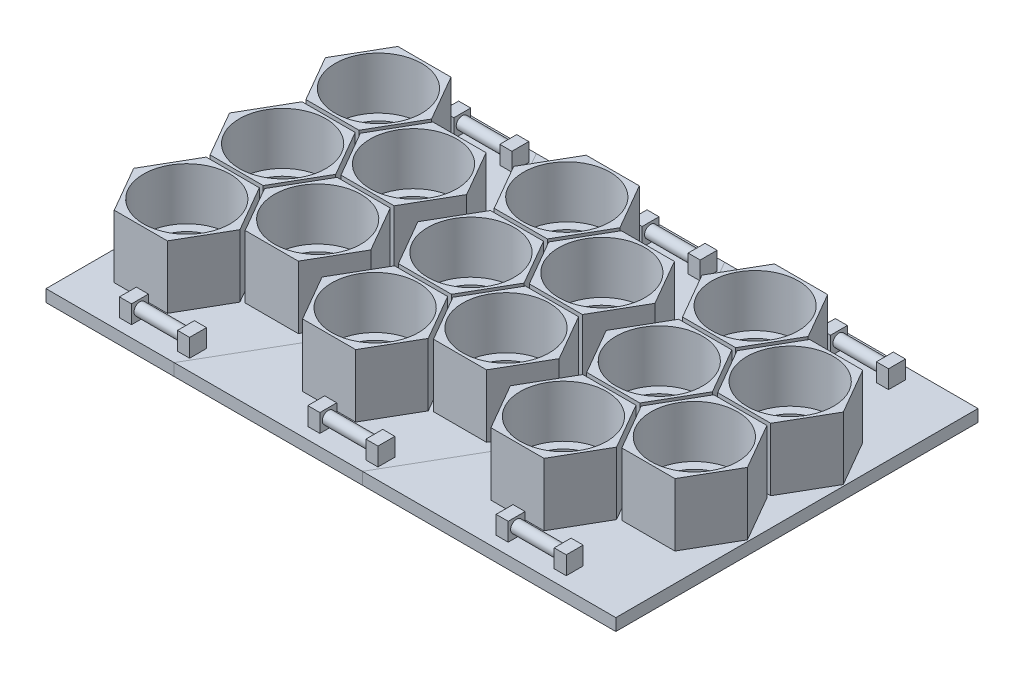
SolidWorks part; units mm, degrees
ref_plane "Front Plane" through (0, 0, 0) normal (0, 0, 1) x (1, 0, 0)
ref_plane "Top Plane" through (0, 0, 0) normal (0, 1, 0) x (1, 0, 0)
ref_plane "Right Plane" through (0, 0, 0) normal (1, 0, 0) x (0, 0, -1)
sketch "Sketch1" plane through (0, 0, 0) normal (0, 1, 0) x (1, 0, 0)
  line L0 (-118, 0) -> (118, 0)
  line L1 (-118, -75) -> (-118, 75)
  line L2 (118, -75) -> (118, 75)
  line L3 (-118, 75) -> (118, 75)
  line L4 (118, -75) -> (-118, -75)
  point P4 (0, 0)
  point P8 (-118, 0)
  point P11 (118, 0)
  dimension "D1" = 236
  dimension "D2" = 150
  dimension "D3" = 150
extrude "Boss-Extrude1" add sketch "Sketch1" along normal mid plane 5 contours L4 L2 L0 L1 | L3 L1 L0 L2 region at (0, 0, -37.5) region at (0, 0, 37.5)
sketch "Sketch3" plane through (0, 2.5, 0) normal (0, 1, 0) x (1, 0, 0)
  line L1 (-84.0015, 58.7375) -> (-105.9985, 58.7375)
  line L2 (-105.9985, 58.7375) -> (-116.997, 39.6875)
  line L3 (-116.997, 39.6875) -> (-105.9985, 20.6375)
  line L4 (-105.9985, 20.6375) -> (-84.0015, 20.6375)
  line L5 (-84.0015, 20.6375) -> (-73.003, 39.6875)
  line L6 (-73.003, 39.6875) -> (-84.0015, 58.7375)
  line L7 (-84.0015, 19.05) -> (-105.9985, 19.05)
  line L8 (-105.9985, 19.05) -> (-116.997, 0)
  line L9 (-116.997, 0) -> (-105.9985, -19.05)
  line L10 (-105.9985, -19.05) -> (-84.0015, -19.05)
  line L11 (-84.0015, -19.05) -> (-73.003, 0)
  line L12 (-73.003, 0) -> (-84.0015, 19.05)
  line L13 (-73.003, -39.6875) -> (-84.0015, -20.6375)
  line L14 (-84.0015, -20.6375) -> (-105.9985, -20.6375)
  line L15 (-105.9985, -20.6375) -> (-116.997, -39.6875)
  line L16 (-116.997, -39.6875) -> (-105.9985, -58.7375)
  line L17 (-105.9985, -58.7375) -> (-84.0015, -58.7375)
  line L18 (-84.0015, -58.7375) -> (-73.003, -39.6875)
  line L31 (-95, -19.05) -> (-95, -20.6375) construction
  line L32 (-105.9985, -58.7375) -> (-116.997, -39.6875)
  line L33 (-73.003, -39.6875) -> (-84.0015, -58.7375)
  line L34 (-84.0015, -20.6375) -> (-73.003, -39.6875)
  line L35 (-116.997, -39.6875) -> (-105.9985, -20.6375)
  line L36 (-116.997, 0) -> (-105.9985, 19.05)
  line L37 (-105.9985, -19.05) -> (-116.997, 0)
  line L38 (-73.003, 0) -> (-84.0015, -19.05)
  line L39 (-84.0015, 19.05) -> (-73.003, 0)
  line L40 (-116.997, 39.6875) -> (-105.9985, 58.7375)
  line L41 (-105.9985, 20.6375) -> (-116.997, 39.6875)
  line L42 (-73.003, 39.6875) -> (-84.0015, 20.6375)
  line L43 (-84.0015, 58.7375) -> (-73.003, 39.6875)
  line L44 (-105.9985, 58.7375) -> (-116.997, 39.6875)
  line L45 (-116.997, 39.6875) -> (-105.9985, 20.6375)
  line L46 (-84.0015, 20.6375) -> (-73.003, 39.6875)
  line L47 (-73.003, 39.6875) -> (-84.0015, 58.7375)
  line L48 (-105.9985, 19.05) -> (-116.997, 0)
  line L49 (-116.997, 0) -> (-105.9985, -19.05)
  line L50 (-84.0015, -19.05) -> (-73.003, 0)
  line L51 (-73.003, 0) -> (-84.0015, 19.05)
  line L52 (-73.003, -39.6875) -> (-84.0015, -20.6375)
  line L53 (-105.9985, -20.6375) -> (-116.997, -39.6875)
  line L54 (-116.997, -39.6875) -> (-105.9985, -58.7375)
  line L55 (-84.0015, -58.7375) -> (-73.003, -39.6875)
  line L56 (-105.9985, -58.7375) -> (-116.997, -39.6875)
  line L57 (-73.003, -39.6875) -> (-84.0015, -58.7375)
  line L58 (-84.0015, -20.6375) -> (-73.003, -39.6875)
  line L59 (-116.997, -39.6875) -> (-105.9985, -20.6375)
  line L60 (-116.997, 0) -> (-105.9985, 19.05)
  line L61 (-105.9985, -19.05) -> (-116.997, 0)
  line L62 (-73.003, 0) -> (-84.0015, -19.05)
  line L63 (-84.0015, 19.05) -> (-73.003, 0)
  line L64 (-116.997, 39.6875) -> (-105.9985, 58.7375)
  line L65 (-105.9985, 20.6375) -> (-116.997, 39.6875)
  line L66 (-73.003, 39.6875) -> (-84.0015, 20.6375)
  line L67 (-84.0015, 58.7375) -> (-73.003, 39.6875)
  line L68 (-105.9985, 58.7375) -> (-116.997, 39.6875)
  line L69 (-116.997, 39.6875) -> (-105.9985, 20.6375)
  line L70 (-84.0015, 20.6375) -> (-73.003, 39.6875)
  line L71 (-73.003, 39.6875) -> (-84.0015, 58.7375)
  line L72 (-105.9985, 19.05) -> (-116.997, 0)
  line L73 (-116.997, 0) -> (-105.9985, -19.05)
  line L74 (-84.0015, -19.05) -> (-73.003, 0)
  line L75 (-73.003, 0) -> (-84.0015, 19.05)
  line L76 (-73.003, -39.6875) -> (-84.0015, -20.6375)
  line L77 (-105.9985, -20.6375) -> (-116.997, -39.6875)
  line L78 (-116.997, -39.6875) -> (-105.9985, -58.7375)
  line L79 (-84.0015, -58.7375) -> (-73.003, -39.6875)
  line L80 (-105.9985, -58.7375) -> (-116.997, -39.6875)
  line L81 (-73.003, -39.6875) -> (-84.0015, -58.7375)
  line L82 (-84.0015, -20.6375) -> (-73.003, -39.6875)
  line L83 (-116.997, -39.6875) -> (-105.9985, -20.6375)
  line L84 (-116.997, 0) -> (-105.9985, 19.05)
  line L85 (-105.9985, -19.05) -> (-116.997, 0)
  line L86 (-73.003, 0) -> (-84.0015, -19.05)
  line L87 (-84.0015, 19.05) -> (-73.003, 0)
  line L88 (-116.997, 39.6875) -> (-105.9985, 58.7375)
  line L89 (-105.9985, 20.6375) -> (-116.997, 39.6875)
  line L90 (-73.003, 39.6875) -> (-84.0015, 20.6375)
  line L91 (-84.0015, 58.7375) -> (-73.003, 39.6875)
  line L92 (-105.9985, 58.7375) -> (-116.997, 39.6875)
  line L93 (-116.997, 39.6875) -> (-105.9985, 20.6375)
  line L94 (-84.0015, 20.6375) -> (-73.003, 39.6875)
  line L95 (-73.003, 39.6875) -> (-84.0015, 58.7375)
  line L96 (-105.9985, 19.05) -> (-116.997, 0)
  line L97 (-116.997, 0) -> (-105.9985, -19.05)
  line L98 (-84.0015, -19.05) -> (-73.003, 0)
  line L99 (-73.003, 0) -> (-84.0015, 19.05)
  line L100 (-73.003, -39.6875) -> (-84.0015, -20.6375)
  line L101 (-105.9985, -20.6375) -> (-116.997, -39.6875)
  line L102 (-116.997, -39.6875) -> (-105.9985, -58.7375)
  line L103 (-84.0015, -58.7375) -> (-73.003, -39.6875)
  line L104 (-105.9985, -58.7375) -> (-116.997, -39.6875)
  line L105 (-73.003, -39.6875) -> (-84.0015, -58.7375)
  line L106 (-84.0015, -20.6375) -> (-73.003, -39.6875)
  line L107 (-116.997, -39.6875) -> (-105.9985, -20.6375)
  line L108 (-116.997, 0) -> (-105.9985, 19.05)
  line L109 (-105.9985, -19.05) -> (-116.997, 0)
  line L110 (-73.003, 0) -> (-84.0015, -19.05)
  line L111 (-84.0015, 19.05) -> (-73.003, 0)
  line L112 (-116.997, 39.6875) -> (-105.9985, 58.7375)
  line L113 (-105.9985, 20.6375) -> (-116.997, 39.6875)
  line L114 (-73.003, 39.6875) -> (-84.0015, 20.6375)
  line L115 (-84.0015, 58.7375) -> (-73.003, 39.6875)
  line L135 (-95, 20.6375) -> (-95, 19.05) construction
  line L136 (-78.5022, -9.525) -> (-77.1274, -10.3188) construction
  line L138 (0, 0) -> (-118, 0) construction
  line L139 (-118, -75) -> (-118, 75) construction
  line L140 (-49.6311, 38.8937) -> (-38.6326, 19.8438)
  line L141 (-38.6326, -19.8438) -> (-49.6311, -0.7938)
  line L142 (-49.6311, -0.7938) -> (-71.6281, -0.7938)
  line L143 (-71.6281, -0.7938) -> (-82.6267, -19.8438)
  line L144 (-82.6267, -19.8438) -> (-71.6281, -38.8938)
  line L145 (-71.6281, -38.8938) -> (-49.6311, -38.8938)
  line L146 (-49.6311, -38.8938) -> (-38.6326, -19.8438)
  line L147 (-71.6281, 38.8937) -> (-49.6311, 38.8937)
  line L148 (-82.6267, 19.8438) -> (-71.6281, 38.8937)
  line L149 (-71.6281, 0.7937) -> (-82.6267, 19.8438)
  line L150 (-49.6311, 0.7938) -> (-71.6281, 0.7937)
  line L151 (-38.6326, 19.8438) -> (-49.6311, 0.7938)
  circle A0 centre (-95, 39.6875) radius 19.05 construction
  circle A1 centre (-95, 0) radius 19.05 construction
  circle A2 centre (-95, -39.6875) radius 19.05 construction
  circle A3 centre (-60.6296, -19.8438) radius 19.05 construction
  dimension "D1" = 38.1
  dimension "D3" = 23
  dimension "D2" = 1.5875
extrude "Boss-Extrude2" add sketch "Sketch3" along normal blind 26 contours L5 L6 L1 L2 L3 L4 | L151 L140 L147 L148 L149 L150 | L11 L12 L7 L8 L9 L10 | L17 L18 L13 L14 L15 L16 | L145 L146 L141 L142 L143 L144 region at (-95, 2.5, -39.6875) region at (-95, 2.5, 0) region at (-95, 2.5, 39.6875) region at (-60.6296, 2.5, -19.8437) region at (-60.6296, 2.5, 19.8438)
sketch "Sketch4" plane through (0, 28.5, 0) normal (0, 1, 0) x (1, 0, 0)
  line L0 (-116.997, 0) -> (-73.003, 0) construction
  line L2 (-116.997, -39.6875) -> (-73.003, -39.6875) construction
  line L3 (-82.6267, 19.8437) -> (-38.6326, 19.8438) construction
  circle A0 centre (-95, 0) radius 13.97
  circle A1 centre (-95, 0) radius 17.907
  circle A2 centre (-95, -39.6875) radius 13.97
  circle A3 centre (-95, -39.6875) radius 17.907
  circle A4 centre (-95, 39.6875) radius 13.97
  circle A5 centre (-95, 39.6875) radius 17.907
  circle A6 centre (-60.6296, 19.8437) radius 13.97
  circle A7 centre (-60.6296, 19.8437) radius 17.907
  circle A8 centre (-60.6296, -19.8437) radius 17.907
  circle A9 centre (-60.6296, -19.8437) radius 13.97
  dimension "D1" = 27.94
  dimension "D2" = 35.814
extrude "Cut-Extrude1" cut sketch "Sketch4" against normal blind 25.4 contours A2 | A0 | A9 | A6 | A4
extrude "Cut-Extrude2" cut sketch "Sketch4<4>" against normal blind 21.5544 contours A3 | A1 | A8 | A7 | A5
sketch "Sketch4<4>" plane through (0, 28.5, 0) normal (0, 1, 0) x (1, 0, 0) same geometry as "Sketch4"
pattern_linear "LPattern1" count 3 spacing 78 along (1, 0, 0) of "Boss-Extrude2", "Cut-Extrude1", "Cut-Extrude2"
sketch "Sketch10" plane through (0, 2.5, 0) normal (0, 1, 0) x (1, 0, 0)
  line L0 (-95, -66.7375) -> (-60.6296, -66.7375) construction
  line L1 (-87.3398, -66.7375) -> (-68.2898, -66.7375) construction
  line L2 (-87.3398, -70.2375) -> (-87.3398, -63.2375)
  line L3 (-105.9985, -58.7375) -> (-84.0015, -58.7375) construction
  line L4 (-87.3398, -63.2375) -> (-92.3398, -63.2375)
  line L5 (-92.3398, -63.2375) -> (-92.3398, -70.2375)
  line L6 (-92.3398, -70.2375) -> (-87.3398, -70.2375)
  line L7 (-68.2898, -70.2375) -> (-68.2898, -63.2375)
  line L8 (-68.2898, -63.2375) -> (-63.2898, -63.2375)
  line L9 (-63.2898, -63.2375) -> (-63.2898, -70.2375)
  line L10 (-63.2898, -70.2375) -> (-68.2898, -70.2375)
  circle A1 centre (-95, -39.6875) radius 13.97 construction
  point P14 (-77.8148, -66.7375)
  point P16 (-87.3398, -66.7375)
  point P21 (-68.2898, -66.7375)
  dimension "D1" = 19.05
  dimension "D2" = 8
  dimension "D3" = 7
  dimension "D4" = 5
extrude "Boss-Extrude7" add sketch "Sketch10" along normal blind 7.5
sketch "Sketch12" plane through (-87.3398, 0, 0) normal (1, 0, 0) x (0, 0, -1)
  line L0 (-70.2375, 10) -> (-66.7375, 10) construction
  line L1 (-70.2375, 10) -> (-63.2375, 10) construction
  line L2 (-66.7375, 10) -> (-66.7375, 6.5) construction
  circle A0 centre (-66.7375, 6.5) radius 2.5
  dimension "D1" = 5
extrude "Boss-Extrude8" add sketch "Sketch12" along normal up to surface (19.05 mm away) up to face at (-68.2898, 6.25, 66.7375)
mirror "Mirror1" about plane through (0, 0, 0) normal (0, 0, 1) of "Boss-Extrude7", "Boss-Extrude8"
pattern_linear "LPattern2" count 3 spacing 78 along (1, 0, 0) of "Mirror1"
sketch "Sketch9" plane through (0, 2.5, 0) normal (0, 1, 0) x (1, 0, 0)
  line L0 (-39.6981, -21.6892) -> (-31.3788, -26.4924) construction
  line L1 (-49.6311, -38.8938) -> (-38.6326, -19.8438) construction
  line L2 (-27.9985, -20.6375) -> (-38.997, -39.6875) construction
  line L3 (-35.5722, -5.932) -> (-43.8914, -10.7352) construction
  line L4 (-38.997, 0) -> (-27.9985, -19.05) construction
  line L5 (-38.6326, -19.8438) -> (-49.6311, -0.7938) construction
  line L6 (-44.1318, 10.3187) -> (-35.8126, 5.5156) construction
  line L7 (-38.6326, 19.8438) -> (-49.6311, 0.7938) construction
  line L8 (-27.9985, 19.05) -> (-38.997, 0) construction
  line L9 (-44.1318, 29.3688) -> (-35.8126, 34.1719) construction
  line L11 (-38.997, 39.6875) -> (-27.9985, 20.6375) construction
  line L12 (-39.9722, 31.7703) -> (-33.0864, 19.8437)
  line L13 (-39.9722, 7.9172) -> (-33.0864, 19.8437)
  line L14 (-39.9722, 7.9172) -> (-44.5432, 0)
  line L15 (-49.6311, 38.8937) -> (-38.6326, 19.8438) construction
  line L16 (-38.997, 39.6875) -> (-27.9985, 20.6375) construction
  line L17 (-27.9985, 19.05) -> (-38.997, 0) construction
  line L18 (-39.7318, -8.3336) -> (-44.5432, 0)
  line L19 (-35.5384, -24.0908) -> (-33.0864, -19.8438)
  line L20 (-39.7318, -8.3336) -> (-33.0864, -19.8438)
  line L21 (-38.6326, -19.8438) -> (-49.6311, -0.7938) construction
  line L22 (-39.9722, 31.7703) -> (-64.9309, 75)
  line L23 (-118, 75) -> (118, 75) construction
  line L24 (-35.5384, -24.0908) -> (-64.9309, -75)
  line L25 (118, -75) -> (-118, -75) construction
  line L26 (37.81, 22.5413) -> (46.1292, 27.3444) construction
  line L27 (28.3689, 38.8937) -> (39.3674, 19.8438) construction
  line L28 (39.003, 39.6875) -> (50.0015, 20.6375) construction
  line L30 (33.8682, 10.3188) -> (42.1874, 5.5156) construction
  line L31 (50.0015, 19.05) -> (39.003, 0) construction
  line L32 (47.6867, -15.0406) -> (39.3674, -19.8438) construction
  line L33 (39.003, 0) -> (50.0015, -19.05) construction
  line L34 (39.3674, -19.8438) -> (28.3689, -0.7938) construction
  line L35 (39.3674, -19.8438) -> (28.3689, -0.7938) construction
  line L36 (33.8682, -29.3687) -> (42.1874, -34.1719) construction
  line L38 (50.0015, -20.6375) -> (39.003, -39.6875) construction
  line L39 (28.3689, 38.8937) -> (39.3674, 19.8438) construction
  line L40 (39.3674, 19.8438) -> (28.3689, 0.7938) construction
  line L41 (39.3674, 19.8438) -> (28.3689, 0.7938) construction
  line L42 (28.3689, -38.8938) -> (39.3674, -19.8438) construction
  line L43 (41.9696, 24.9429) -> (13.0691, 75)
  line L44 (41.9696, 24.9429) -> (44.9136, 19.8438)
  line L45 (38.0278, 7.9172) -> (44.9136, 19.8438)
  line L46 (38.0278, 7.9172) -> (33.4568, 0)
  line L47 (33.4568, 0) -> (43.527, -17.4422)
  line L48 (43.527, -17.4422) -> (44.9136, -19.8437)
  line L49 (38.0278, -31.7703) -> (13.0691, -75)
  line L50 (44.9136, -19.8437) -> (38.0278, -31.7703)
split "Split1" trim tools "Sketch9" bodies to split 123 resulting bodies 124 125 126
delete or keep bodies "Body-Delete/Keep 1" [suppressed] type delete bodies bodies 125 126
delete or keep bodies "Body-Delete/Keep 2" [suppressed] type delete bodies bodies 124 126
delete or keep bodies "Body-Delete/Keep 3" [suppressed] type delete bodies bodies 124 125
